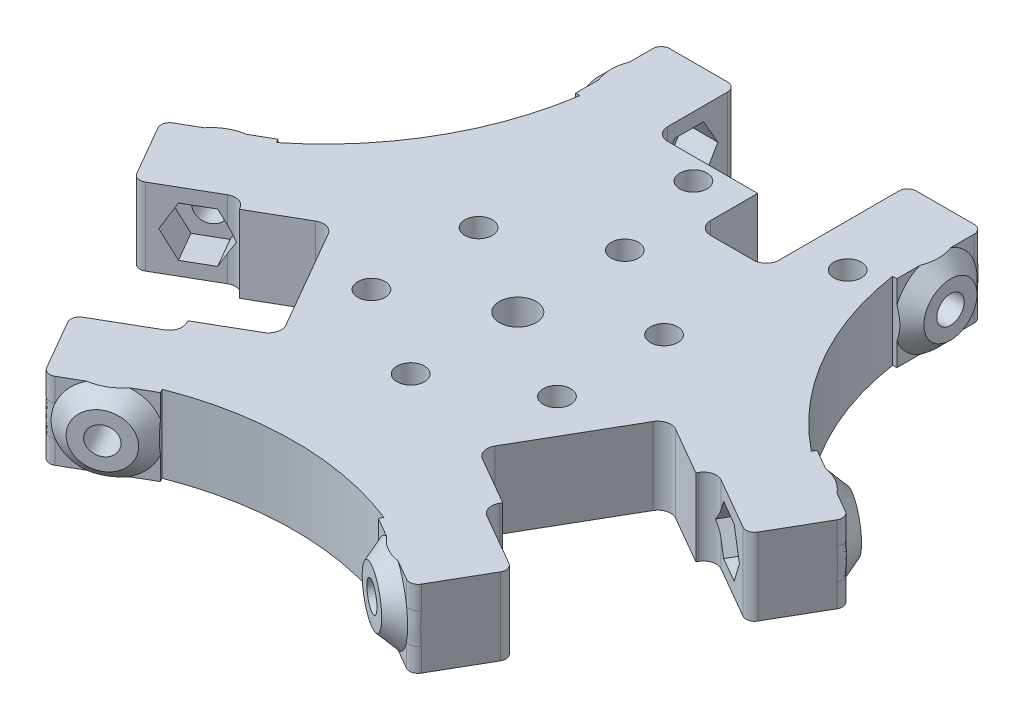
SolidWorks part; units mm, degrees
ref_plane "Front Plane" through (0, 0, 0) normal (0, 0, 1) x (1, 0, 0)
ref_plane "Top Plane" through (0, 0, 0) normal (0, 1, 0) x (1, 0, 0)
ref_plane "Right Plane" through (0, 0, 0) normal (1, 0, 0) x (0, 0, -1)
sketch "Sketch1" plane through (0, 0, 0) normal (0, 1, 0) x (1, 0, 0)
  line L0 (-17, 30) -> (17, 30) construction
  line L1 (0, -54.6431) -> (0, 54.6431) construction
  line L2 (-18.6, 34.5) -> (18.6, 34.5)
  line L3 (18.6, 34.5) -> (20.5, 32.6)
  line L4 (20.5, 32.6) -> (20.5, 31.6)
  line L5 (0, 35.7149) -> (0, 30) construction
  line L6 (-20.5, 32.6) -> (-20.5, 31.6)
  line L7 (-18.6, 34.5) -> (-20.5, 32.6)
  line L8 (-20.5, 31.6) -> (20.5, 31.6)
  point P2 (0, 30)
  point P15 (0, 34.5)
  dimension "D1" = 30
  dimension "D2" = 34
  dimension "D3" = 3.2
  dimension "D4" = 9
  dimension "D5" = 45
  dimension "D6" = 20.5
  dimension "D7" = 1
revolve "Revolve1" add sketch "Sketch1" angle 360 about L0
sketch "Sketch2" plane through (0, 0, 0) normal (0, 1, 0) x (1, 0, 0)
  line L0 (-20.5, 27.4) -> (20.5, 27.4) construction
  line L1 (0, 0) -> (0, 32.7452) construction
  line L2 (-4, 3.2438) -> (-4, 27.4)
  line L3 (-4, 27.4) -> (4, 27.4)
  line L4 (4, 3.2438) -> (4, 27.4)
  line L5 (0, -54.6431) -> (0, 54.6431) construction
  circle A0 centre (0, 0) radius 2.15
  arc A1 (-4, 3.2438) -> (4, 3.2438) centre (0, 0) ccw
  circle A3 centre (0, 0) radius 5.15 construction
  point P11 (11.15, 0)
  dimension "D1" = 4.3
  dimension "D3" = 8
  dimension "D2" = 3
extrude "Boss-Extrude2" add sketch "Sketch2" along normal mid plane 4.5
pattern_circular "CirPattern1" count 3 over 360 about axis through (0, 2.25, 0) along (0, -1, 0) of "Boss-Extrude2", "Revolve1"
sketch "Sketch3" plane through (0, 0, 0) normal (0, 1, 0) x (1, 0, 0)
  line L0 (0, 0) -> (-53.2606, 30.75) construction
  line L1 (-4, 26.1029) -> (-4, 3.2438) construction
  line L2 (-4.8092, 1.8422) -> (-24.6058, -9.5873) construction
  line L3 (-17.2684, 30) -> (0, 30)
  line L4 (0, -54.6431) -> (0, 54.6431) construction
  line L5 (0, 30) -> (0, 2.15)
  line L6 (-1.862, -1.075) -> (-25.9808, -15)
  line L7 (-20.5, 30) -> (20.5, 30) construction
  line L8 (-25.9808, -15) -> (-34.6149, -0.0451)
  line L9 (20.5, 27.4) -> (20.5, 32.6) construction
  arc A0 (-34.6149, -0.0451) -> (-17.2684, 30) centre (-53.2606, 30.75) ccw
  circle A1 centre (0, 0) radius 2.15 construction
  arc A2 (0, 2.15) -> (-1.862, -1.075) centre (0, 0) ccw
  dimension "D1" = 36
  dimension "D2" = 61.5
extrude "Boss-Extrude3" add sketch "Sketch3" against normal mid plane 9
sketch "Sketch9" plane through (0, 0, 0) normal (1, 0, 0) x (0, 0, -1)
  circle A0 centre (30, 0) radius 2.55
  circle A1 centre (30, 0) radius 1.6 construction
  dimension "D1" = 5.1
extrude "Cut-Extrude5" cut sketch "Sketch9" against normal mid plane 37.2
pattern_circular "CirPattern3" count 3 over 360 about axis through (0, 2.25, 0) along (0, -1, 0) of "Cut-Extrude5", "Boss-Extrude3"
sketch "Sketch10" plane through (0, 0, 0) normal (1, 0, 0) x (0, 0, -1)
  line L1 (34.5, 4.5) -> (25.5, 4.5)
  line L2 (34.5, 4.5) -> (34.5, -4.5)
  line L3 (34.5, -4.5) -> (25.5, -4.5)
  line L4 (25.5, 4.5) -> (25.5, -4.5)
  line L5 (34.5, 4.5) -> (25.5, -4.5) construction
  line L6 (34.5, -4.5) -> (25.5, 4.5) construction
  circle A0 centre (30, 0) radius 4.5 construction
  point P0 (30, 0)
extrude "Boss-Extrude4" add sketch "Sketch10" along normal mid plane 41
pattern_circular "CirPattern10" count 3 over 360 about axis through (0, 2.25, 0) along (0, -1, 0) of "Boss-Extrude4"
sketch "Sketch11" plane through (0, 0, 0) normal (0, 1, 0) x (1, 0, 0)
  line L0 (15.7308, -32.7535) -> (36.2308, 2.7535) construction
  line L3 (38.7324, 1.8865) -> (39.556, -1.187)
  line L6 (39.556, -1.187) -> (41.4047, -2.2544)
  line L7 (41.4047, -2.2544) -> (44.0665, 2.3561)
  line L8 (44.0665, 2.3561) -> (40.2693, 4.5484)
  line L9 (40.2693, 4.5484) -> (38.7324, 1.8865)
  line L10 (0, 0) -> (25.9808, -15) construction
  line L11 (16.1956, -37.1484) -> (17.7324, -34.4865)
  line L12 (19.9928, -39.3408) -> (16.1956, -37.1484)
  line L13 (22.6547, -34.7303) -> (19.9928, -39.3408)
  line L14 (20.806, -33.663) -> (22.6547, -34.7303)
  line L15 (17.7324, -34.4865) -> (20.806, -33.663)
revolve "Cut-Revolve1" cut sketch "Sketch11" angle 360 about L0
sketch "Sketch12" plane through (10.25, 0, -17.7535) normal (0.5, 0, -0.866) x (-0.866, 0, -0.5)
  circle A0 centre (-30, 0) radius 1.6
  dimension "D1" = 3.2
extrude "Cut-Extrude6" cut sketch "Sketch12" against normal through all
sketch "Sketch13" plane through (0, 4.5, 0) normal (0, 1, 0) x (1, 0, 0)
  line L0 (28.8157, -5.0897) -> (40.074, -11.5897)
  line L1 (26.7667, -5.6388) -> (19.5167, -18.1962)
  line L2 (18.8157, -22.4103) -> (30.074, -28.9103)
  line L3 (30.074, -28.9103) -> (40.074, -11.5897)
  line L5 (0, 0) -> (36.4498, -21.0443) construction
  line L6 (19.9186, -11.5) -> (24.3706, -14.0704) construction
  line L9 (19.5167, -18.1962) -> (18.2667, -20.3612)
  line L11 (20.5029, -33.488) -> (39.2529, -1.012) construction
  arc A0 (18.8157, -22.4103) -> (18.2667, -20.3612) centre (19.5657, -21.1112) cw
  arc A1 (28.8157, -5.0897) -> (26.7667, -5.6388) centre (28.0657, -6.3888) ccw
  circle A2 centre (0, 0) radius 26 construction
  point P16 (21.9681, -12.6833)
  dimension "D1" = 1.5
  dimension "D2" = 52
  dimension "D3" = 20
  dimension "D5" = 23
  dimension "D7" = 6
extrude "Cut-Extrude7" cut sketch "Sketch13" against normal through all
pattern_circular "CirPattern11" count 3 over 360 about axis through (0, 2.25, 0) along (0, -1, 0) of "Cut-Extrude6", "Cut-Revolve1", "Cut-Extrude7"
sketch "Sketch14" plane through (0, 0, 0) normal (1, 0, 0) x (0, 0, -1)
  line L1 (31.6743, 2.9) -> (28.3257, 2.9)
  line L2 (28.3257, 2.9) -> (26.6514, 0)
  line L3 (26.6514, 0) -> (28.3257, -2.9)
  line L4 (28.3257, -2.9) -> (31.6743, -2.9)
  line L5 (31.6743, -2.9) -> (33.3486, 0)
  line L6 (33.3486, 0) -> (31.6743, 2.9)
  circle A0 centre (30, 0) radius 3.3486 construction
  circle A1 centre (30, 0) radius 1.6 construction
  dimension "D1" = 5.8
extrude "Cut-Extrude8" cut sketch "Sketch14" against normal mid plane 28
sketch "Sketch15" plane through (0, -4.5, 0) normal (0, -1, 0) x (1, 0, 0)
  circle A0 centre (0, 0) radius 8.15
  dimension "D1" = 16.3
extrude "Cut-Extrude9" cut sketch "Sketch15" against normal blind 4
sketch "Sketch16" plane through (0, -4.5, 0) normal (0, -1, 0) x (1, 0, 0)
  line L1 (10.8253, 6.25) -> (0, 12.5) construction
  line L2 (0, 12.5) -> (-10.8253, 6.25) construction
  line L3 (-10.8253, 6.25) -> (-10.8253, -6.25) construction
  line L4 (-10.8253, -6.25) -> (0, -12.5) construction
  line L5 (0, -12.5) -> (10.8253, -6.25) construction
  line L6 (10.8253, -6.25) -> (10.8253, 6.25) construction
  line L7 (6.25, 10.8253) -> (-6.25, 10.8253) construction
  line L8 (-6.25, 10.8253) -> (-12.5, 0) construction
  line L9 (-12.5, 0) -> (-6.25, -10.8253) construction
  line L10 (-6.25, -10.8253) -> (6.25, -10.8253) construction
  line L11 (6.25, -10.8253) -> (12.5, 0) construction
  line L12 (12.5, 0) -> (6.25, 10.8253) construction
  circle A0 centre (0, 0) radius 10.8253 construction
  circle A1 centre (0, 12.5) radius 1.6
  circle A2 centre (10.8253, 6.25) radius 1.6
  circle A3 centre (10.8253, -6.25) radius 1.6
  circle A4 centre (0, -12.5) radius 1.6
  circle A5 centre (-10.8253, -6.25) radius 1.6
  circle A6 centre (-10.8253, 6.25) radius 1.6
  circle A7 centre (0, 0) radius 10.8253 construction
  circle A8 centre (6.25, 10.8253) radius 1.6 construction
  circle A9 centre (-6.25, 10.8253) radius 1.6 construction
  circle A10 centre (-12.5, 0) radius 1.6 construction
  circle A11 centre (12.5, 0) radius 1.6 construction
  circle A12 centre (6.25, -10.8253) radius 1.6 construction
  circle A13 centre (-6.25, -10.8253) radius 1.6 construction
  dimension "D2" = 3.2
  dimension "D1" = 25
  dimension "D3" = 25
extrude "Cut-Extrude10" cut sketch "Sketch16" against normal through all
sketch "Sketch17" plane through (0, 4.5, 0) normal (0, 1, 0) x (1, 0, 0)
  line L0 (0, 0) -> (0, 35.7645) construction
  line L1 (15, 23.5) -> (-3, 23.5) construction
  line L2 (6, 16.3866) -> (6, 33.1082) construction
  line L3 (10, 27.5) -> (10, 34.5) construction
  line L4 (10, 27.5) -> (2, 27.5)
  line L5 (10, 27.5) -> (10, 20.5)
  line L6 (8.5, 19) -> (3.5, 19)
  line L7 (2, 27.5) -> (2, 20.5)
  line L8 (-8.5, 26) -> (8.5, 26) construction
  circle A0 centre (15, 23.5) radius 1.6
  circle A1 centre (-3, 23.5) radius 1.6
  circle A2 centre (15.0182, -20.9826) radius 1.6 construction
  circle A3 centre (24.0417, -5.4078) radius 1.6 construction
  circle A4 centre (-25.6806, -2.5149) radius 1.6 construction
  circle A5 centre (-16.7041, -18.1169) radius 1.6 construction
  arc A6 (8.5, 26) -> (10, 27.5) centre (8.5, 27.5) ccw construction
  arc A7 (10, 20.5) -> (8.5, 19) centre (8.5, 20.5) cw
  arc A8 (3.5, 19) -> (2, 20.5) centre (3.5, 20.5) cw
  point P17 (0, 0)
  dimension "D1" = 3.2
  dimension "D6" = 1.5
  dimension "D2" = 18
  dimension "D3" = 23.5
  dimension "D4" = 6
  dimension "D5" = 7
pattern_circular "CirPattern15" count 3 over 360 about axis through (0, 2.25, 0) along (0, -1, 0) of "Cut-Extrude8"
extrude "Cut-Extrude11" cut sketch "Sketch17" against normal through all
sketch "Sketch18" plane through (0, 4.5, 0) normal (0, 1, 0) x (1, 0, 0)
  line L0 (0, 23) -> (0, 32.4138) construction
  line L1 (-8.5, 26) -> (2, 26) construction
  line L2 (-8.25, 26) -> (8.25, 26) construction
  line L3 (-8.25, 26) -> (-8.25, 19.5) construction
  line L4 (-6.75, 18) -> (6.75, 18) construction
  line L5 (8.25, 26) -> (8.25, 19.5) construction
  line L6 (0, 0) -> (22.0836, 12.75) construction
  line L7 (0, 0) -> (-22.0836, 12.75) construction
  line L8 (-18.3917, -20.1447) -> (-12.7625, -16.8947)
  line L9 (-18.9635, -3.1543) -> (-12.2135, -14.8457)
  line L10 (-26.6417, -5.8553) -> (-21.0125, -2.6053)
  line L11 (-26.6417, -5.8553) -> (-18.3917, -20.1447)
  line L12 (26.6417, -5.8553) -> (21.0125, -2.6053)
  line L13 (12.2135, -14.8457) -> (18.9635, -3.1543)
  line L14 (18.3917, -20.1447) -> (12.7625, -16.8947)
  line L15 (18.3917, -20.1447) -> (26.6417, -5.8553)
  arc A0 (6.75, 18) -> (8.25, 19.5) centre (6.75, 19.5) ccw construction
  arc A1 (-8.25, 19.5) -> (-6.75, 18) centre (-6.75, 19.5) ccw construction
  arc A2 (17.6454, 25.5) -> (30.9064, 2.5314) centre (53.2606, 30.75) ccw construction
  arc A3 (-30.9064, 2.5314) -> (-17.6454, 25.5) centre (-53.2606, 30.75) ccw construction
  arc A4 (-21.0125, -2.6053) -> (-18.9635, -3.1543) centre (-20.2625, -3.9043) cw
  arc A5 (-12.2135, -14.8457) -> (-12.7625, -16.8947) centre (-13.5125, -15.5957) cw
  arc A6 (12.7625, -16.8947) -> (12.2135, -14.8457) centre (13.5125, -15.5957) cw
  arc A7 (18.9635, -3.1543) -> (21.0125, -2.6053) centre (20.2625, -3.9043) cw
  point P12 (8.25, 18)
  dimension "D3" = 1.5
  dimension "D1" = 16.5
  dimension "D2" = 8
other "Move Face2" face at (-23.1798, 0, -13.3828) face at (0, 0, 26.7657) face at (23.1798, 0, -13.3828) offset 0.6 parameters "D1"=0.6
other "Move Face3" face at (21.9353, -0.0993, 31.0069) face at (37.8231, -0.0412, 3.4884) face at (15.8889, 0.0646, -34.5) face at (-15.8889, 0.0646, -34.5) face at (-37.8231, 0.0412, 3.4884) face at (-21.9353, 0.0993, 31.0069) offset 1 parameters "D1"=1
fillet "Fillet2" radius 1 12 edges at (25.7439, 0, 26.4103) (35.7439, 0, 9.0897) (40.1189, 0, 1.512) (21.3689, 0, 33.988) (-21.3689, 0, 33.988) (-40.1189, 0, 1.512) (18.75, 0, -35.5) (-18.75, 0, -35.5) (-10, 0, -35.5) (10, 0, -35.5) (-35.7439, 0, 9.0897) (-25.7439, 0, 26.4103)
sketch "Sketch19" plane through (0, -4.5, 0) normal (0, -1, 0) x (1, 0, 0)
  line L0 (15.7308, 32.7535) -> (36.2308, -2.7535)
  line L1 (18.4154, 34.3035) -> (13.0461, 31.2035) construction
  line L2 (33.5461, -4.3035) -> (38.9154, -1.2035) construction
  line L3 (0, 0) -> (25.9808, 15)
  line L4 (-20.5, -30) -> (20.5, -30)
  line L5 (-20.5, -26.9) -> (-20.5, -33.1) construction
  line L6 (20.5, -33.1) -> (20.5, -26.9) construction
  line L7 (0, -30) -> (0, 0)
  dimension "D1" = 30
extrude "Cut-Extrude12" cut sketch "Sketch18" against normal through all
